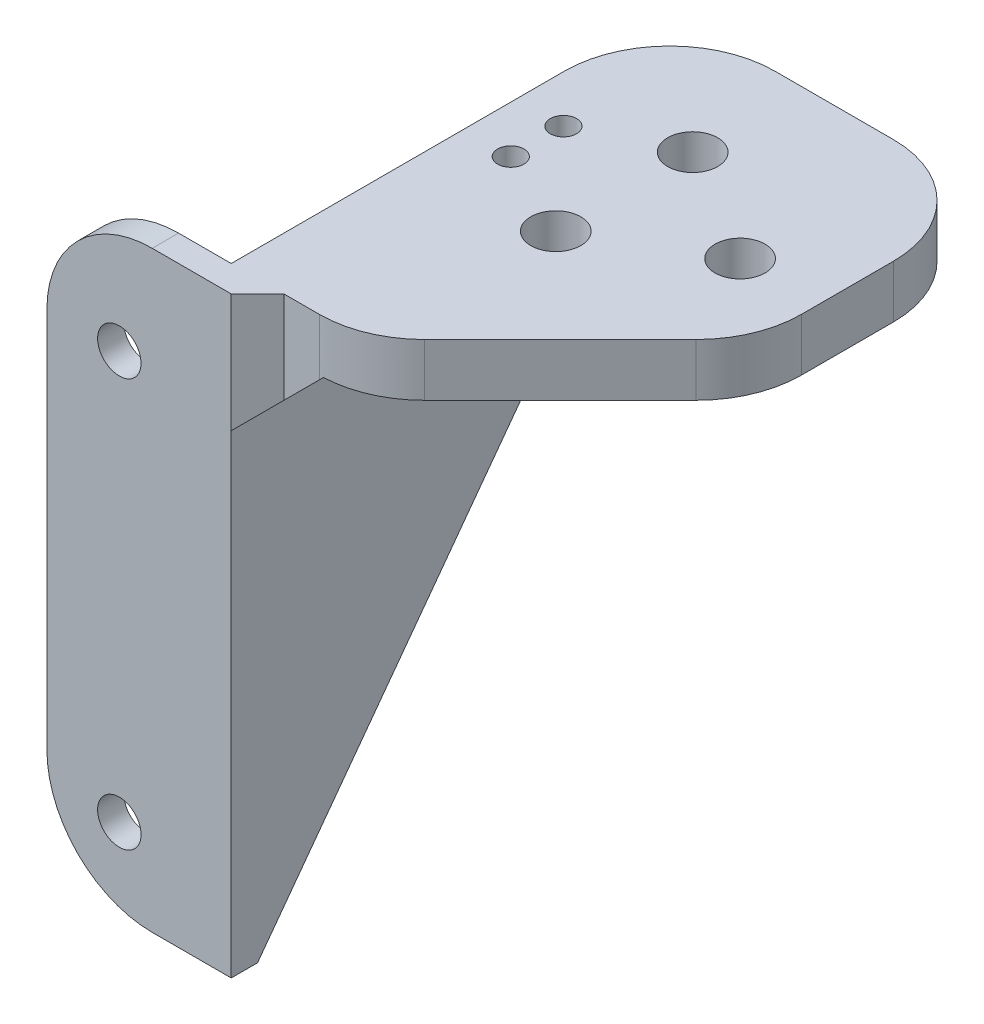
SolidWorks part; units mm, degrees
ref_plane "Front Plane" through (0, 0, 0) normal (0, 0, 1) x (1, 0, 0)
ref_plane "Top Plane" through (0, 0, 0) normal (0, 1, 0) x (1, 0, 0)
ref_plane "Right Plane" through (0, 0, 0) normal (1, 0, 0) x (0, 0, -1)
sketch "Sketch1" plane through (0, 0, 0) normal (0, 0, 1) x (1, 0, 0)
  line L0 (-6.5, 37) -> (-6.5, 6) construction
  line L1 (0, 0) -> (-12, 0)
  line L2 (0, 0) -> (0, 45)
  line L3 (0, 45) -> (-12, 45)
  line L4 (-12, 0) -> (-12, 45)
  circle A0 centre (-6.5, 37) radius 1.65
  circle A1 centre (-6.5, 6) radius 1.65
  dimension "D6" = 3.3
  dimension "D1" = 31
  dimension "D2" = 12
  dimension "D3" = 6.5
  dimension "D4" = 6
  dimension "D5" = 45
extrude "Boss-Extrude1" add sketch "Sketch1" against normal blind 2
sketch "Sketch2" plane through (0, 0, 0) normal (1, 0, 0) x (0, 0, -1)
  line L0 (35.3, 45) -> (2, 0)
  line L1 (0, 45) -> (35.3, 45)
  line L2 (0, 45) -> (0, 0)
  line L3 (0, 0) -> (2, 0)
  line L5 (2, 0) -> (2, 45) construction
  line L6 (2, 0) -> (0, 0) construction
  dimension "D1" = 35.3
extrude "Boss-Extrude2" add sketch "Sketch2" along normal blind 2
sketch "Sketch3" plane through (0, 45, 0) normal (0, 1, 0) x (1, 0, 0)
  line L0 (0, 2) -> (-12, 2) construction
  line L1 (0, 35.3) -> (25, 35.3)
  line L2 (0, 35.3) -> (0, 2)
  line L3 (0, 2) -> (25, 2)
  line L4 (25, 35.3) -> (25, 2)
  dimension "D1" = 25
  dimension "D2" = 33.3
extrude "Boss-Extrude3" add sketch "Sketch3" against normal blind 4
sketch "Sketch4" plane through (0, 45, 0) normal (0, 1, 0) x (1, 0, 0)
  line L1 (6.2, 32.85) -> (24, 32.85) construction
  line L2 (6.2, 32.85) -> (6.2, 10.45) construction
  line L3 (6.2, 10.45) -> (24, 10.45) construction
  line L4 (24, 32.85) -> (24, 10.45) construction
  line L5 (6.2, 21.65) -> (24, 21.65) construction
  line L6 (12.5, 35.3) -> (12.5, 2) construction
  line L7 (25, 35.3) -> (0, 35.3) construction
  line L8 (2, 2) -> (25, 2) construction
  line L11 (25, 2) -> (25, 35.3) construction
  circle A0 centre (10.2, 26.85) radius 1.9
  circle A1 centre (10.2, 16.45) radius 1.9
  circle A2 centre (19, 21.65) radius 1.9
  dimension "D3" = 3.8
  dimension "D1" = 17.8
  dimension "D2" = 22.4
  dimension "D4" = 4
  dimension "D5" = 6
  dimension "D6" = 6
  dimension "D7" = 4
  dimension "D8" = 5
  dimension "D9" = 1
  dimension "D10" = 8.45
extrude "Cut-Extrude1" cut sketch "Sketch4" against normal up to surface (4 mm away) up to face at (9, 41, -23.2133)
sketch "Sketch5" plane through (0, 45, 0) normal (0, 1, 0) x (1, 0, 0)
  line L0 (0, 21.65) -> (25, 21.65) construction
  line L1 (0, 35.3) -> (0, 2) construction
  line L3 (3.5826, 23.65) -> (3.5826, 19.65) construction
  circle A0 centre (3.5826, 23.65) radius 1
  circle A1 centre (3.5826, 19.65) radius 1
  circle A2 centre (19, 21.65) radius 1.9 construction
  circle A3 centre (19, 21.65) radius 1.9
  dimension "D1" = 2
  dimension "D2" = 4
extrude "Cut-Extrude2" cut sketch "Sketch5" against normal through all
sketch "Sketch6" plane through (0, 45, 0) normal (0, 1, 0) x (1, 0, 0)
  line L0 (10, 2) -> (25, 17)
  line L1 (2, 2) -> (25, 2) construction
  line L2 (25, 2) -> (25, 35.3) construction
  line L3 (25, 17) -> (25, 2)
  line L4 (25, 2) -> (10, 2)
  dimension "D1" = 45
  dimension "D2" = 15
extrude "Cut-Extrude3" cut sketch "Sketch6" against normal up to surface (4 mm away) up to face at (3.5826, 41, -18.65)
chamfer "Chamfer1" distance 5 angle 45 1 edges at (2, 41, -17.17)
chamfer "Chamfer2" distance 2 angle 45 1 edges at (2, 40.5, -2)
fillet "Fillet1" radius 8 2 edges at (-12, 0, -1) (-12, 45, -1)
fillet "Fillet2" radius 8 2 edges at (0, 43, -35.3) (25, 43, -35.3)
fillet "Fillet3" radius 8 2 edges at (10, 43, -2) (25, 43, -17)
